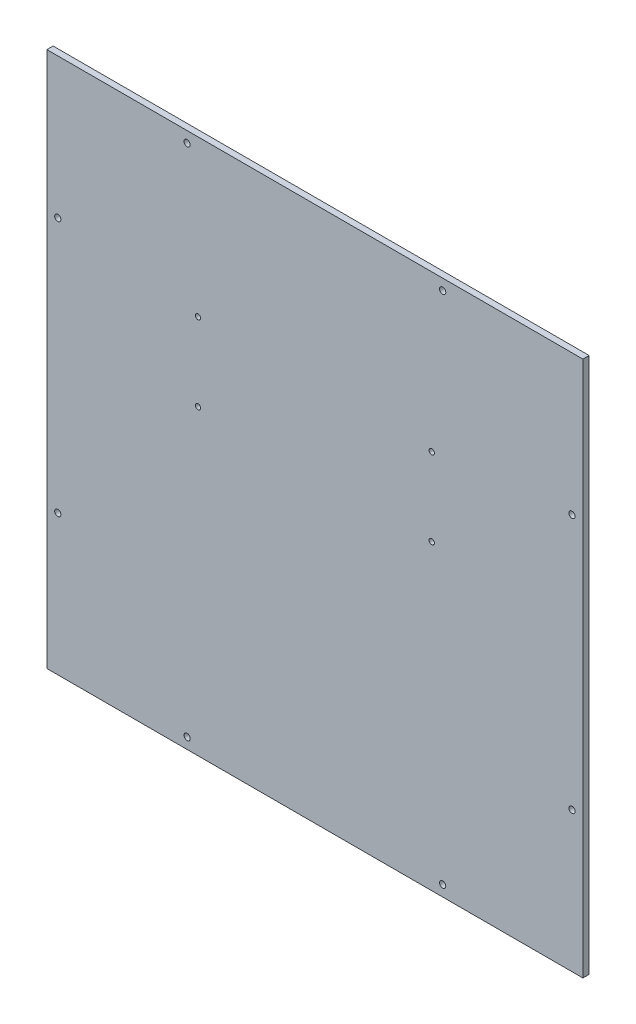
SolidWorks part; units mm, degrees
ref_plane "Piano frontale" through (0, 0, 0) normal (0, 0, 1) x (1, 0, 0)
ref_plane "Piano superiore" through (0, 0, 0) normal (0, 1, 0) x (1, 0, 0)
ref_plane "Piano destro" through (0, 0, 0) normal (1, 0, 0) x (0, 0, -1)
sketch "Schizzo1" plane through (0, 0, 0) normal (0, 0, 1) x (1, 0, 0)
  line L0 (0, 0) -> (0, 344)
  line L1 (0, 344) -> (344, 344)
  line L2 (344, 344) -> (344, 0)
  line L3 (344, 0) -> (0, 0)
  line L4 (0, 172) -> (344, 172) construction
  line L5 (172, 42) -> (172, 123.488) construction
  circle A0 centre (90, 337) radius 2
  circle A1 centre (254, 337) radius 2
  circle A2 centre (337, 254) radius 2
  circle A3 centre (7, 254) radius 2
  circle A4 centre (337, 90) radius 2
  circle A5 centre (254, 7) radius 2
  circle A6 centre (90, 7) radius 2
  circle A7 centre (7, 90) radius 2
  dimension "D3" = 4
  dimension "D4" = 7
  dimension "D6" = 7
  dimension "D5" = 90
  dimension "D1" = 344
  dimension "D2" = 344
  dimension "D7" = 90
extrude "Estrusione-Estrusione1" add sketch "Schizzo1" along normal blind 4
sketch "Schizzo2" plane through (0, 0, 4) normal (0, 0, 1) x (1, 0, 0)
  line L1 (344, 344) -> (0, 344) construction
  line L2 (172, 344) -> (172, 0) construction
  line L3 (0, 0) -> (344, 0) construction
  circle A0 centre (97, 244) radius 1.7
  circle A1 centre (97, 194) radius 1.7
  circle A2 centre (247, 244) radius 1.7
  circle A3 centre (247, 194) radius 1.7
  dimension "D1" = 150
  dimension "D2" = 100
  dimension "D3" = 3.4
  dimension "D4" = 50
extrude "Taglio-Estrusione1" cut sketch "Schizzo2" against normal through all
